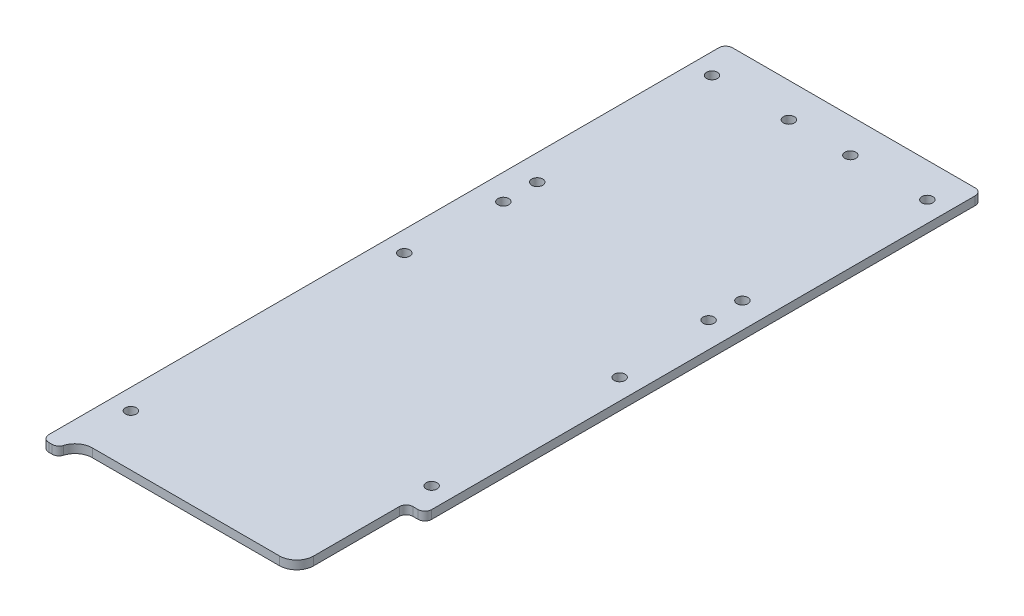
SolidWorks part; units mm, degrees
ref_plane "Front Plane" through (0, 0, 0) normal (0, 0, 1) x (1, 0, 0)
ref_plane "Top Plane" through (0, 0, 0) normal (0, 1, 0) x (1, 0, 0)
ref_plane "Right Plane" through (0, 0, 0) normal (1, 0, 0) x (0, 0, -1)
sketch "Sketch1" plane through (0, 0, 0) normal (0, 1, 0) x (1, 0, 0)
  line L0 (-39.9997, 0) -> (-39.9997, 114.3) construction
  line L1 (-47.625, 127) -> (47.625, 127)
  line L2 (-47.625, 127) -> (-47.625, -127)
  line L3 (-47.625, -127) -> (47.625, -127)
  line L4 (47.625, 127) -> (47.625, -127)
  line L5 (-47.625, 127) -> (47.625, -127) construction
  line L6 (-47.625, -127) -> (47.625, 127) construction
  line L7 (0, 0) -> (0, 127) construction
  line L8 (-39.9997, 0) -> (-39.9997, -101.6) construction
  line L9 (-39.9997, 0) -> (0, 0) construction
  line L10 (-41.275, -127) -> (-41.275, -120.65)
  line L11 (-41.275, -120.65) -> (41.275, -120.65)
  line L12 (41.275, -120.65) -> (41.275, -127)
  line L13 (-39.9997, 114.3) -> (-11.4247, 114.3) construction
  line L14 (39.9997, 114.3) -> (11.4247, 114.3) construction
  circle A0 centre (-39.9997, 114.3) radius 2.032
  circle A1 centre (-39.9997, 0) radius 2.032
  circle A2 centre (-39.9997, -101.6) radius 2.032
  circle A3 centre (39.9997, -101.6) radius 2.032
  circle A4 centre (39.9997, 0) radius 2.032
  circle A5 centre (39.9997, 114.3) radius 2.032
  circle A6 centre (-11.4247, 114.3) radius 2.032
  circle A7 centre (11.4247, 114.3) radius 2.032
  circle A8 centre (-39.9997, -69.85) radius 2.032
  circle A9 centre (39.9997, -69.85) radius 2.032
  point P0 (0, 0)
  dimension "D4" = 4.064
  dimension "D10" = 28.575
  dimension "D1" = 95.25
  dimension "D2" = 254
  dimension "D3" = 7.6253
  dimension "D5" = 12.7
  dimension "D6" = 25.4
  dimension "D7" = 6.35
  dimension "D8" = 6.35
  dimension "D9" = 6.35
  dimension "D11" = 69.85
extrude "Boss-Extrude1" add sketch "Sketch1" along normal blind 3.175 contours L4 L1 L2 L3 A4 A0 A1 A2 A3 A5 | A8 | A3 region at (0, 0, -2.6944) region at (39.9997, 0, 101.6) region at (-39.9997, 0, 69.85)
fillet "Fillet1" radius 2.54 4 edges at (-47.625, 1.5875, -127) (47.625, 1.5875, -127) (47.625, 1.5875, 127) (-47.625, 1.5875, 127)
fillet "Fillet2" radius 2.54 2 edges at (41.275, 1.5875, 127) (-41.275, 1.5875, 127)
fillet "Fillet3" radius 6.35 2 edges at (41.275, 1.5875, 120.65) (-41.275, 1.5875, 120.65)
sketch "Sketch2" plane through (0, 0, 0) normal (0, -1, 0) x (1, 0, 0)
  line L0 (41.9102, 131.8831) -> (41.9102, 109.8659) construction
  line L1 (41.9102, 109.8659) -> (41.9102, 106.3879) construction
  line L2 (41.9102, 83.271) -> (41.9102, 82.5325) construction
  line L3 (41.9102, 82.5325) -> (41.9102, 81.2514) construction
  line L4 (41.9102, 83.271) -> (41.9102, 106.3879) construction
  line L5 (41.9102, 131.8831) -> (41.9102, 109.8659)
  line L6 (41.9102, 109.8659) -> (41.9102, 106.3879)
  line L7 (41.9102, 83.271) -> (41.9102, 82.5325)
  line L8 (41.9102, 82.5325) -> (41.9102, 81.2514)
  line L9 (41.9102, 83.271) -> (41.9102, 106.3879)
  line L10 (41.9102, 81.2514) -> (47.625, 81.2514)
  line L11 (47.625, -124.46) -> (47.625, 124.46) construction
  line L12 (41.9102, 131.8831) -> (47.625, 131.8831)
  line L13 (47.625, 131.8831) -> (47.625, 81.2514)
  line L14 (40.6402, 79.9814) -> (48.895, 79.9814)
  line L15 (48.895, 133.1531) -> (48.895, 79.9814)
  line L16 (40.6402, 133.1531) -> (48.895, 133.1531)
  line L17 (40.6402, 133.1531) -> (40.6402, 109.8659)
  line L18 (40.6402, 109.8659) -> (40.6402, 106.3879)
  line L19 (40.6402, 83.271) -> (40.6402, 106.3879)
  line L20 (40.6402, 83.271) -> (40.6402, 82.5325)
  line L21 (40.6402, 82.5325) -> (40.6402, 79.9814)
  arc M7 (43.815, 127) -> (41.3809, 125.1857) centre (43.815, 124.46) ccw
  arc M8 (41.3809, 125.1857) -> (35.2956, 120.65) centre (35.2956, 127) cw
  line M18 (47.625, -124.46) -> (47.625, 124.46)
  dimension "D1" = 1.27
extrude "Cut-Extrude1" cut sketch "Sketch2" against normal through all contours L20 L21 L14 L10 L8 L7 L9 L19 M18 | L19 L9 L6 L5 L17 L18 M7 M8 | L13 L10 L8 L7 L9 L6 L5 L12 region at (41.6754, 0, 99.9791)
fillet "Fillet4" radius 6.35 1 edges at (40.6402, 1.5875, 123.5711)
fillet "Fillet5" radius 2.54 2 edges at (47.625, 1.5875, 79.9814) (40.6402, 1.5875, 79.9814)
sketch "Sketch3" plane through (0, 0, 0) normal (0, -1, 0) x (1, 0, 0)
  line L0 (-36.3103, -49.7791) -> (-39.9171, -49.7791) construction
  line L1 (-40.4251, -49.276) -> (-40.4251, -45.7043) construction
  line L2 (-35.8023, -45.7043) -> (-35.8023, -49.276) construction
  line L3 (-39.9171, -45.2013) -> (-36.3103, -45.2013) construction
  line L4 (-36.3103, -37.2027) -> (-39.9171, -37.2027) construction
  line L5 (-35.8023, -33.1279) -> (-35.8023, -36.6996) construction
  line L6 (-40.4251, -36.6996) -> (-40.4251, -33.1279) construction
  line L7 (-39.9171, -32.6249) -> (-36.3103, -32.6249) construction
  line L8 (36.2829, -32.6249) -> (39.8897, -32.6249) construction
  line L9 (40.3977, -33.1279) -> (40.3977, -36.6996) construction
  line L10 (39.8897, -37.2027) -> (36.2829, -37.2027) construction
  line L11 (35.7749, -36.6996) -> (35.7749, -33.1279) construction
  line L12 (36.2829, -45.2013) -> (39.8897, -45.2013) construction
  line L13 (35.7749, -49.276) -> (35.7749, -45.7043) construction
  line L14 (40.3977, -45.7043) -> (40.3977, -49.276) construction
  line L15 (39.8897, -49.7791) -> (36.2829, -49.7791) construction
  line L16 (-36.3103, -49.7791) -> (-39.9171, -49.7791)
  line L17 (-40.4251, -49.276) -> (-40.4251, -45.7043)
  line L18 (-35.8023, -45.7043) -> (-35.8023, -49.276)
  line L19 (-39.9171, -45.2013) -> (-36.3103, -45.2013)
  line L20 (-36.3103, -37.2027) -> (-39.9171, -37.2027)
  line L21 (-35.8023, -33.1279) -> (-35.8023, -36.6996)
  line L22 (-40.4251, -36.6996) -> (-40.4251, -33.1279)
  line L23 (-39.9171, -32.6249) -> (-36.3103, -32.6249)
  line L24 (36.2829, -32.6249) -> (39.8897, -32.6249)
  line L25 (40.3977, -33.1279) -> (40.3977, -36.6996)
  line L26 (39.8897, -37.2027) -> (36.2829, -37.2027)
  line L27 (35.7749, -36.6996) -> (35.7749, -33.1279)
  line L28 (36.2829, -45.2013) -> (39.8897, -45.2013)
  line L29 (35.7749, -49.276) -> (35.7749, -45.7043)
  line L30 (40.3977, -45.7043) -> (40.3977, -49.276)
  line L31 (39.8897, -49.7791) -> (36.2829, -49.7791)
  line L32 (-47.625, -25.836) -> (47.625, -25.836)
  line L33 (-47.625, -124.46) -> (-47.625, 124.46) construction
  line L34 (47.625, -124.46) -> (47.625, 77.4414) construction
  line L35 (0, -25.836) -> (0, -56.0686) construction
  line L38 (134.3605, -51.414) -> (184.1363, -51.414)
  line L39 (184.1363, -51.414) -> (184.1363, -43.4909)
  line L40 (184.1363, -43.4909) -> (182.3329, -43.4909)
  line L41 (181.8249, -42.9878) -> (181.8249, -39.4161)
  line L42 (182.3329, -38.9131) -> (184.1363, -38.9131)
  line L43 (184.1363, -38.9131) -> (184.1363, -30.9899)
  line L44 (184.1363, -30.9899) -> (134.3605, -30.9899)
  line L45 (134.3605, -30.9899) -> (133.3363, -32.0041)
  line L46 (133.3363, -32.0041) -> (132.3121, -30.9899)
  line L47 (132.3121, -30.9899) -> (70.8605, -30.9899)
  line L48 (70.8605, -30.9899) -> (69.8363, -32.0041)
  line L49 (69.8363, -32.0041) -> (68.8121, -30.9899)
  line L50 (68.8121, -30.9899) -> (7.3605, -30.9899)
  line L51 (7.3605, -30.9899) -> (6.3363, -32.0041)
  line L52 (6.3363, -32.0041) -> (5.3121, -30.9899)
  line L53 (5.3121, -30.9899) -> (-56.1395, -30.9899)
  line L54 (-56.1395, -30.9899) -> (-57.1637, -32.0041)
  line L55 (-57.1637, -32.0041) -> (-58.1879, -30.9899)
  line L56 (-58.1879, -30.9899) -> (-119.6395, -30.9899)
  line L57 (-119.6395, -30.9899) -> (-120.6637, -32.0041)
  line L58 (-120.6637, -32.0041) -> (-121.6879, -30.9899)
  line L59 (-121.6879, -30.9899) -> (-184.1637, -30.9899)
  line L60 (-184.1637, -30.9899) -> (-184.1637, -51.414)
  line L61 (-184.1637, -51.414) -> (-121.6879, -51.414)
  line L62 (-121.6879, -51.414) -> (-120.6637, -50.3998)
  line L63 (-120.6637, -50.3998) -> (-119.6395, -51.414)
  line L64 (-119.6395, -51.414) -> (-58.1879, -51.414)
  line L65 (-58.1879, -51.414) -> (-57.1637, -50.3998)
  line L66 (-57.1637, -50.3998) -> (-56.1395, -51.414)
  line L67 (-56.1395, -51.414) -> (5.3121, -51.414)
  line L68 (5.3121, -51.414) -> (6.3363, -50.3998)
  line L69 (6.3363, -50.3998) -> (7.3605, -51.414)
  line L70 (7.3605, -51.414) -> (68.8121, -51.414)
  line L71 (68.8121, -51.414) -> (69.8363, -50.3998)
  line L72 (69.8363, -50.3998) -> (70.8605, -51.414)
  line L73 (70.8605, -51.414) -> (132.3121, -51.414)
  line L74 (132.3121, -51.414) -> (133.3363, -50.3998)
  line L75 (133.3363, -50.3998) -> (134.3605, -51.414)
  line L76 (134.3605, -51.414) -> (184.1363, -51.414)
  line L77 (184.1363, -51.414) -> (184.1363, -43.4909)
  line L78 (184.1363, -43.4909) -> (182.3329, -43.4909)
  line L79 (181.8249, -42.9878) -> (181.8249, -39.4161)
  line L80 (182.3329, -38.9131) -> (184.1363, -38.9131)
  line L81 (184.1363, -38.9131) -> (184.1363, -30.9899)
  line L82 (184.1363, -30.9899) -> (134.3605, -30.9899)
  line L83 (134.3605, -30.9899) -> (133.3363, -32.0041)
  line L84 (133.3363, -32.0041) -> (132.3121, -30.9899)
  line L85 (132.3121, -30.9899) -> (70.8605, -30.9899)
  line L86 (70.8605, -30.9899) -> (69.8363, -32.0041)
  line L87 (69.8363, -32.0041) -> (68.8121, -30.9899)
  line L88 (68.8121, -30.9899) -> (7.3605, -30.9899)
  line L89 (7.3605, -30.9899) -> (6.3363, -32.0041)
  line L90 (6.3363, -32.0041) -> (5.3121, -30.9899)
  line L91 (5.3121, -30.9899) -> (-56.1395, -30.9899)
  line L92 (-56.1395, -30.9899) -> (-57.1637, -32.0041)
  line L93 (-57.1637, -32.0041) -> (-58.1879, -30.9899)
  line L94 (-58.1879, -30.9899) -> (-119.6395, -30.9899)
  line L95 (-119.6395, -30.9899) -> (-120.6637, -32.0041)
  line L96 (-120.6637, -32.0041) -> (-121.6879, -30.9899)
  line L97 (-121.6879, -30.9899) -> (-184.1637, -30.9899)
  line L98 (-184.1637, -30.9899) -> (-184.1637, -51.414)
  line L99 (-184.1637, -51.414) -> (-121.6879, -51.414)
  line L100 (-121.6879, -51.414) -> (-120.6637, -50.3998)
  line L101 (-120.6637, -50.3998) -> (-119.6395, -51.414)
  line L102 (-119.6395, -51.414) -> (-58.1879, -51.414)
  line L103 (-58.1879, -51.414) -> (-57.1637, -50.3998)
  line L104 (-57.1637, -50.3998) -> (-56.1395, -51.414)
  line L105 (-56.1395, -51.414) -> (5.3121, -51.414)
  line L106 (5.3121, -51.414) -> (6.3363, -50.3998)
  line L107 (6.3363, -50.3998) -> (7.3605, -51.414)
  line L108 (7.3605, -51.414) -> (68.8121, -51.414)
  line L109 (68.8121, -51.414) -> (69.8363, -50.3998)
  line L110 (69.8363, -50.3998) -> (70.8605, -51.414)
  line L111 (70.8605, -51.414) -> (132.3121, -51.414)
  line L112 (132.3121, -51.414) -> (133.3363, -50.3998)
  line L113 (133.3363, -50.3998) -> (134.3605, -51.414)
  line L1362 (-40.4251, -34.9138) -> (-35.8023, -34.9138)
  line L1857 (-38.1137, -32.6249) -> (-38.1137, -37.2027)
  line L1858 (-38.1137, -45.2013) -> (-38.1137, -49.7791)
  line L1859 (-40.4251, -47.4902) -> (-35.8023, -47.4902)
  circle A0 centre (-38.1137, -34.9138) radius 2.032
  circle A1 centre (-38.1137, -47.4902) radius 2.032
  circle A2 centre (38.1137, -47.4902) radius 2.032
  circle A3 centre (38.1137, -34.9138) radius 2.032
  ellipse E0 centre (-39.9171, -45.7043) end of major axis (-39.4091, -45.7043) minor radius 0.5031 (-39.9171, -45.2013) -> (-40.4251, -45.7043) ccw construction
  ellipse E1 centre (-39.9171, -49.276) end of major axis (-39.4091, -49.276) minor radius 0.5031 (-40.4251, -49.276) -> (-39.9171, -49.7791) ccw construction
  ellipse E2 centre (182.3329, -42.9878) end of major axis (182.8409, -42.9878) minor radius 0.5031 (181.8249, -42.9878) -> (182.3329, -43.4909) ccw
  ellipse E3 centre (182.3329, -39.4161) end of major axis (182.8409, -39.4161) minor radius 0.5031 (182.3329, -38.9131) -> (181.8249, -39.4161) ccw
  ellipse E4 centre (182.3329, -42.9878) end of major axis (182.8409, -42.9878) minor radius 0.5031 (181.8249, -42.9878) -> (182.3329, -43.4909) ccw
  ellipse E5 centre (182.3329, -39.4161) end of major axis (182.8409, -39.4161) minor radius 0.5031 (182.3329, -38.9131) -> (181.8249, -39.4161) ccw
  ellipse E6 centre (-36.3103, -49.276) end of major axis (-35.8023, -49.276) minor radius 0.5031 (-36.3103, -49.7791) -> (-35.8023, -49.276) ccw construction
  ellipse E7 centre (-36.3103, -45.7043) end of major axis (-35.8023, -45.7043) minor radius 0.5031 (-35.8023, -45.7043) -> (-36.3103, -45.2013) ccw construction
  ellipse E8 centre (-39.9171, -36.6996) end of major axis (-39.4091, -36.6996) minor radius 0.5031 (-40.4251, -36.6996) -> (-39.9171, -37.2027) ccw construction
  ellipse E9 centre (-36.3103, -36.6996) end of major axis (-35.8023, -36.6996) minor radius 0.5031 (-36.3103, -37.2027) -> (-35.8023, -36.6996) ccw construction
  ellipse E10 centre (-36.3103, -33.1279) end of major axis (-35.8023, -33.1279) minor radius 0.5031 (-35.8023, -33.1279) -> (-36.3103, -32.6249) ccw construction
  ellipse E11 centre (-39.9171, -33.1279) end of major axis (-39.4091, -33.1279) minor radius 0.5031 (-39.9171, -32.6249) -> (-40.4251, -33.1279) ccw construction
  ellipse E12 centre (39.8897, -33.1279) end of major axis (40.3977, -33.1279) minor radius 0.5031 (40.3977, -33.1279) -> (39.8897, -32.6249) ccw construction
  ellipse E13 centre (36.2829, -33.1279) end of major axis (36.7909, -33.1279) minor radius 0.5031 (36.2829, -32.6249) -> (35.7749, -33.1279) ccw construction
  ellipse E14 centre (39.8897, -36.6996) end of major axis (40.3977, -36.6996) minor radius 0.5031 (39.8897, -37.2027) -> (40.3977, -36.6996) ccw construction
  ellipse E15 centre (36.2829, -36.6996) end of major axis (36.7909, -36.6996) minor radius 0.5031 (35.7749, -36.6996) -> (36.2829, -37.2027) ccw construction
  ellipse E16 centre (36.2829, -45.7043) end of major axis (36.7909, -45.7043) minor radius 0.5031 (36.2829, -45.2013) -> (35.7749, -45.7043) ccw construction
  ellipse E17 centre (36.2829, -49.276) end of major axis (36.7909, -49.276) minor radius 0.5031 (35.7749, -49.276) -> (36.2829, -49.7791) ccw construction
  ellipse E18 centre (39.8897, -45.7043) end of major axis (40.3977, -45.7043) minor radius 0.5031 (40.3977, -45.7043) -> (39.8897, -45.2013) ccw construction
  ellipse E19 centre (39.8897, -49.276) end of major axis (40.3977, -49.276) minor radius 0.5031 (39.8897, -49.7791) -> (40.3977, -49.276) ccw construction
  ellipse E20 centre (-39.9171, -45.7043) end of major axis (-39.4091, -45.7043) minor radius 0.5031 (-39.9171, -45.2013) -> (-40.4251, -45.7043) ccw
  ellipse E21 centre (-39.9171, -49.276) end of major axis (-39.4091, -49.276) minor radius 0.5031 (-40.4251, -49.276) -> (-39.9171, -49.7791) ccw
  ellipse E22 centre (-36.3103, -49.276) end of major axis (-35.8023, -49.276) minor radius 0.5031 (-36.3103, -49.7791) -> (-35.8023, -49.276) ccw
  ellipse E23 centre (-36.3103, -45.7043) end of major axis (-35.8023, -45.7043) minor radius 0.5031 (-35.8023, -45.7043) -> (-36.3103, -45.2013) ccw
  ellipse E24 centre (-39.9171, -36.6996) end of major axis (-39.4091, -36.6996) minor radius 0.5031 (-40.4251, -36.6996) -> (-39.9171, -37.2027) ccw
  ellipse E25 centre (-36.3103, -36.6996) end of major axis (-35.8023, -36.6996) minor radius 0.5031 (-36.3103, -37.2027) -> (-35.8023, -36.6996) ccw
  ellipse E26 centre (-36.3103, -33.1279) end of major axis (-35.8023, -33.1279) minor radius 0.5031 (-35.8023, -33.1279) -> (-36.3103, -32.6249) ccw
  ellipse E27 centre (-39.9171, -33.1279) end of major axis (-39.4091, -33.1279) minor radius 0.5031 (-39.9171, -32.6249) -> (-40.4251, -33.1279) ccw
  ellipse E28 centre (39.8897, -33.1279) end of major axis (40.3977, -33.1279) minor radius 0.5031 (40.3977, -33.1279) -> (39.8897, -32.6249) ccw
  ellipse E29 centre (36.2829, -33.1279) end of major axis (36.7909, -33.1279) minor radius 0.5031 (36.2829, -32.6249) -> (35.7749, -33.1279) ccw
  ellipse E30 centre (39.8897, -36.6996) end of major axis (40.3977, -36.6996) minor radius 0.5031 (39.8897, -37.2027) -> (40.3977, -36.6996) ccw
  ellipse E31 centre (36.2829, -36.6996) end of major axis (36.7909, -36.6996) minor radius 0.5031 (35.7749, -36.6996) -> (36.2829, -37.2027) ccw
  ellipse E32 centre (36.2829, -45.7043) end of major axis (36.7909, -45.7043) minor radius 0.5031 (36.2829, -45.2013) -> (35.7749, -45.7043) ccw
  ellipse E33 centre (36.2829, -49.276) end of major axis (36.7909, -49.276) minor radius 0.5031 (35.7749, -49.276) -> (36.2829, -49.7791) ccw
  ellipse E34 centre (39.8897, -45.7043) end of major axis (40.3977, -45.7043) minor radius 0.5031 (40.3977, -45.7043) -> (39.8897, -45.2013) ccw
  ellipse E35 centre (39.8897, -49.276) end of major axis (40.3977, -49.276) minor radius 0.5031 (39.8897, -49.7791) -> (40.3977, -49.276) ccw
  dimension "D2" = 4.064
  dimension "D1" = 0
extrude "Cut-Extrude2" cut sketch "Sketch3" against normal through all contours A0 | A1 | A2 | A3
